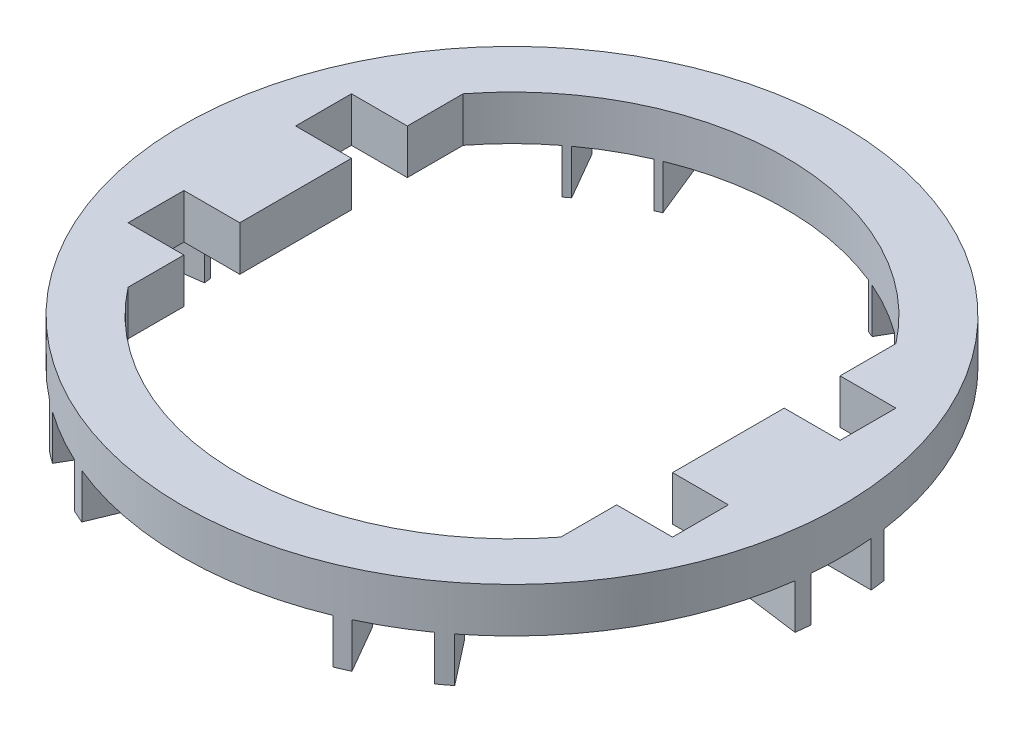
SolidWorks part; units mm, degrees
ref_plane "Front Plane" through (0, 0, 0) normal (0, 0, 1) x (1, 0, 0)
ref_plane "Top Plane" through (0, 0, 0) normal (0, 1, 0) x (1, 0, 0)
ref_plane "Right Plane" through (0, 0, 0) normal (1, 0, 0) x (0, 0, -1)
sketch "Sketch1" plane through (0, 0, 0) normal (0, 1, 0) x (1, 0, 0)
  line L2 (48.5304, 6.7678) -> (58.4345, 8.149)
  line L3 (18.4041, 45.4124) -> (22.1601, 54.6803)
  line L5 (29.9044, 38.8166) -> (36.0074, 46.7383)
  line L6 (48.5683, -6.4897) -> (58.4802, -7.8142)
  line L7 (58.7366, 5.569) -> (48.6825, 5.569)
  line L8 (58.7676, -5.231) -> (48.72, -5.231)
  line L9 (24.5454, 53.6519) -> (19.5184, 44.9448)
  line L10 (33.914, 48.2788) -> (28.8902, 39.5772)
  line L12 (30.1263, -38.6446) -> (36.2745, -46.5313)
  line L13 (18.6639, -45.3063) -> (22.4729, -54.5525)
  line L14 (34.1911, -48.0829) -> (29.1641, -39.3758)
  line L15 (24.8536, -53.5098) -> (19.8298, -44.8083)
  line L32 (-18.4041, -45.4124) -> (-22.1601, -54.6803) [skipped]
  line L33 (-29.9044, -38.8166) -> (-36.0074, -46.7383) [skipped]
  line L34 (-24.5454, -53.6519) -> (-19.5184, -44.9448) [skipped]
  line L35 (-33.914, -48.2788) -> (-28.8902, -39.5772) [skipped]
  line L37 (-48.5304, -6.7678) -> (-58.4345, -8.149) [skipped]
  line L38 (-48.5683, 6.4897) -> (-58.4802, 7.8142) [skipped]
  line L39 (-58.7366, -5.569) -> (-48.6825, -5.569) [skipped]
  line L40 (-58.7676, 5.231) -> (-48.72, 5.231) [skipped]
  line L42 (-30.1263, 38.6446) -> (-36.2745, 46.5313) [skipped]
  line L43 (-18.6639, 45.3063) -> (-22.4729, 54.5525) [skipped]
  line L44 (-34.1911, 48.0829) -> (-29.1641, 39.3758) [skipped]
  line L45 (-24.8536, 53.5098) -> (-19.8298, 44.8083) [skipped]
  arc A0 (22.4729, -54.5525) -> (24.8536, -53.5098) centre (0, 0) ccw
  arc A1 (18.6639, -45.3063) -> (19.8298, -44.8083) centre (0, 0) ccw
  arc A2 (36.0074, 46.7383) -> (33.914, 48.2788) centre (0, 0) ccw
  arc A3 (29.9044, 38.8166) -> (28.8902, 39.5772) centre (0, 0) ccw
  arc A4 (58.4802, -7.8142) -> (58.7676, -5.231) centre (0, 0) ccw
  arc A5 (48.5683, -6.4897) -> (48.72, -5.231) centre (0, 0) ccw
  arc A6 (24.5454, 53.6519) -> (22.1601, 54.6803) centre (0, 0) ccw
  arc A7 (19.5184, 44.9448) -> (18.4041, 45.4124) centre (0, 0) ccw
  arc A8 (58.7366, 5.569) -> (58.4345, 8.149) centre (0, 0) ccw
  arc A9 (48.6825, 5.569) -> (48.5304, 6.7678) centre (0, 0) ccw
  arc A10 (29.1641, -39.3758) -> (30.1263, -38.6446) centre (0, 0) ccw
  arc A11 (34.1911, -48.0829) -> (36.2745, -46.5313) centre (0, 0) ccw
  dimension "D1" = 118
  dimension "D10" = 98
  dimension "D5" = 6
extrude "Boss-Extrude1" add sketch "Sketch1" along normal blind 8
sketch "Sketch2" plane through (0, 8, 0) normal (0, 1, 0) x (1, 0, 0)
  line L0 (22.1601, 54.6803) -> (18.4041, 45.4124)
  line L1 (18.6639, -45.3063) -> (22.4729, -54.5525)
  arc A0 (22.4729, -54.5525) -> (22.1601, 54.6803) centre (0, 0) ccw
  arc A1 (18.6639, -45.3063) -> (18.4041, 45.4124) centre (0, 0) ccw
extrude "Boss-Extrude2" add sketch "Sketch2" along normal blind 8
sketch "Sketch3" plane through (0, 8, 0) normal (0, -1, 0) x (1, 0, 0)
  line L0 (38.7427, -30) -> (38.7427, 30)
  arc A0 (38.7427, -30) -> (38.7427, 30) centre (0, 0) ccw
  dimension "D1" = 98
  dimension "D2" = 60
extrude "Boss-Extrude3" add sketch "Sketch3" against normal blind 8
sketch "Sketch7" plane through (0, 16, 0) normal (0, 1, 0) x (1, 0, 0)
  line L0 (38.7427, -30) -> (38.7427, 30) construction
  line L1 (38.7427, 20) -> (48.7427, 20)
  line L2 (38.7427, 20) -> (38.7427, 10)
  line L3 (38.7427, 10) -> (48.7427, 10)
  line L4 (48.7427, 20) -> (48.7427, 10)
  line L6 (38.7427, -10) -> (48.7427, -10)
  line L7 (38.7427, -10) -> (38.7427, -20)
  line L8 (38.7427, -20) -> (48.7427, -20)
  line L9 (48.7427, -10) -> (48.7427, -20)
  dimension "D1" = 10
  dimension "D2" = 10
  dimension "D3" = 10
  dimension "D4" = 10
  dimension "D5" = 10
  dimension "D6" = 10
extrude "Cut-Extrude1" cut sketch "Sketch7" against normal blind 70
sketch "Sketch8" plane through (0, 16, 0) normal (0, 1, 0) x (1, 0, 0)
  line L0 (38.7427, -30) -> (38.7427, -20)
  line L1 (-38.7427, -30) -> (-38.7427, -20)
  line L2 (38.7427, 20) -> (48.7427, 20)
  line L3 (48.7427, 20) -> (48.7427, 10)
  line L4 (48.7427, 10) -> (38.7427, 10)
  line L5 (38.7427, -10) -> (48.7427, -10)
  line L6 (48.7427, -10) -> (48.7427, -20)
  line L7 (48.7427, -20) -> (38.7427, -20)
  line L8 (38.7427, -10) -> (38.7427, 10)
  line L9 (38.7427, 20) -> (38.7427, 30)
  line L10 (0, -49) -> (0, 49) construction
  line L11 (-38.7427, 20) -> (-38.7427, 30)
  line L12 (-38.7427, -10) -> (-38.7427, 10)
  line L13 (-48.7427, -20) -> (-38.7427, -20)
  line L14 (-48.7427, -10) -> (-48.7427, -20)
  line L15 (-38.7427, -10) -> (-48.7427, -10)
  line L16 (-48.7427, 10) -> (-38.7427, 10)
  line L17 (-48.7427, 20) -> (-48.7427, 10)
  line L18 (-38.7427, 20) -> (-48.7427, 20)
  line L19 (-38.7427, -30) -> (-38.7427, -20)
  line L20 (-38.7427, -10) -> (-38.7427, 10)
  line L21 (-38.7427, 20) -> (-38.7427, 30)
  circle A0 centre (0, 0) radius 59
  arc A1 (38.7427, 30) -> (-38.7427, 30) centre (0, 0) ccw
  arc A2 (-38.7427, -30) -> (38.7427, -30) centre (0, 0) ccw
  line M22 (18.6639, -45.3063) -> (22.4729, -54.5525)
  line M24 (22.1601, 54.6803) -> (18.4041, 45.4124)
  dimension "D1" = 118
  dimension "D2" = 98
extrude "Boss-Extrude4" add sketch "Sketch8" against normal blind 8 contours A2 L1 L13 L14 L15 L12 L16 L17 L18 L11 A1 A0 M24 M22 region at (19.2425, 16, 50.4755)
sketch "Sketch9" plane through (0, 0, 0) normal (0, -1, 0) x (1, 0, 0)
  line L1 (-18.4041, -45.4124) -> (-22.1601, -54.6803)
  line L2 (-29.9044, -38.8166) -> (-36.0074, -46.7383)
  line L3 (-48.5304, -6.7678) -> (-58.4345, -8.149)
  line L4 (-48.5683, 6.4897) -> (-58.4802, 7.8142)
  line L5 (-30.1263, 38.6446) -> (-36.2745, 46.5313)
  line L6 (34.1911, 48.0829) -> (29.1641, 39.3758)
  line L7 (33.914, -48.2788) -> (28.8902, -39.5772)
  line L8 (29.1641, 39.3758) -> (34.1911, 48.0829) construction
  line L9 (24.8536, 53.5098) -> (19.8298, 44.8083)
  line L10 (58.7366, -5.569) -> (48.6825, -5.569)
  line L11 (48.6825, -5.569) -> (58.7366, -5.569) construction
  line L12 (58.7676, 5.231) -> (48.72, 5.231)
  line L13 (58.7676, 5.231) -> (48.72, 5.231) construction
  line L14 (24.5454, -53.6519) -> (19.5184, -44.9448)
  line L15 (33.914, -48.2788) -> (28.8902, -39.5772) construction
  line L16 (19.5184, -44.9448) -> (24.5454, -53.6519) construction
  line L17 (-18.6639, 45.3063) -> (-22.4729, 54.5525)
  line L18 (18.6639, 45.3063) -> (22.4729, 54.5525)
  line L19 (30.1263, 38.6446) -> (36.2745, 46.5313)
  line L20 (-24.5454, -53.6519) -> (-19.5184, -44.9448)
  line L21 (-58.7676, 5.231) -> (-48.72, 5.231)
  line L22 (48.5683, 6.4897) -> (58.4802, 7.8142)
  line L23 (48.5304, -6.7678) -> (58.4345, -8.149)
  line L24 (-58.7366, -5.569) -> (-48.6825, -5.569)
  line L25 (-24.8536, 53.5098) -> (-19.8298, 44.8083)
  line L26 (29.9044, -38.8166) -> (36.0074, -46.7383)
  line L27 (18.4041, -45.4124) -> (22.1601, -54.6803)
  line L28 (-33.914, -48.2788) -> (-28.8902, -39.5772)
  line L29 (-34.1911, 48.0829) -> (-29.1641, 39.3758)
  arc A0 (18.4041, -45.4124) -> (19.5184, -44.9448) centre (0, 0) ccw
  arc A1 (22.1601, -54.6803) -> (24.5454, -53.6519) centre (0, 0) ccw
  arc A2 (48.72, 5.231) -> (48.5683, 6.4897) centre (0, 0) ccw
  arc A3 (58.7676, 5.231) -> (58.4802, 7.8142) centre (0, 0) ccw
  arc A4 (48.5304, -6.7678) -> (48.6825, -5.569) centre (0, 0) ccw
  arc A5 (58.4345, -8.149) -> (58.7366, -5.569) centre (0, 0) ccw
  arc A6 (28.8902, -39.5772) -> (29.9044, -38.8166) centre (0, 0) ccw
  arc A7 (33.914, -48.2788) -> (36.0074, -46.7383) centre (0, 0) ccw
  arc A8 (30.1263, 38.6446) -> (29.1641, 39.3758) centre (0, 0) ccw
  arc A9 (36.2745, 46.5313) -> (34.1911, 48.0829) centre (0, 0) ccw
  arc A10 (19.8298, 44.8083) -> (18.6639, 45.3063) centre (0, 0) ccw
  arc A11 (24.8536, 53.5098) -> (22.4729, 54.5525) centre (0, 0) ccw
  arc A12 (-24.8536, 53.5098) -> (-22.4729, 54.5525) centre (0, 0) cw
  arc A13 (-19.8298, 44.8083) -> (-18.6639, 45.3063) centre (0, 0) cw
  arc A14 (-36.2745, 46.5313) -> (-34.1911, 48.0829) centre (0, 0) cw
  arc A15 (-30.1263, 38.6446) -> (-29.1641, 39.3758) centre (0, 0) cw
  arc A16 (-33.914, -48.2788) -> (-36.0074, -46.7383) centre (0, 0) cw
  arc A17 (-28.8902, -39.5772) -> (-29.9044, -38.8166) centre (0, 0) cw
  arc A18 (-58.4345, -8.149) -> (-58.7366, -5.569) centre (0, 0) cw
  arc A19 (-48.5304, -6.7678) -> (-48.6825, -5.569) centre (0, 0) cw
  arc A20 (-58.7676, 5.231) -> (-58.4802, 7.8142) centre (0, 0) cw
  arc A21 (-48.72, 5.231) -> (-48.5683, 6.4897) centre (0, 0) cw
  arc A22 (-22.1601, -54.6803) -> (-24.5454, -53.6519) centre (0, 0) cw
  arc A23 (-18.4041, -45.4124) -> (-19.5184, -44.9448) centre (0, 0) cw
extrude "Boss-Extrude5" add sketch "Sketch9" against normal blind 8
